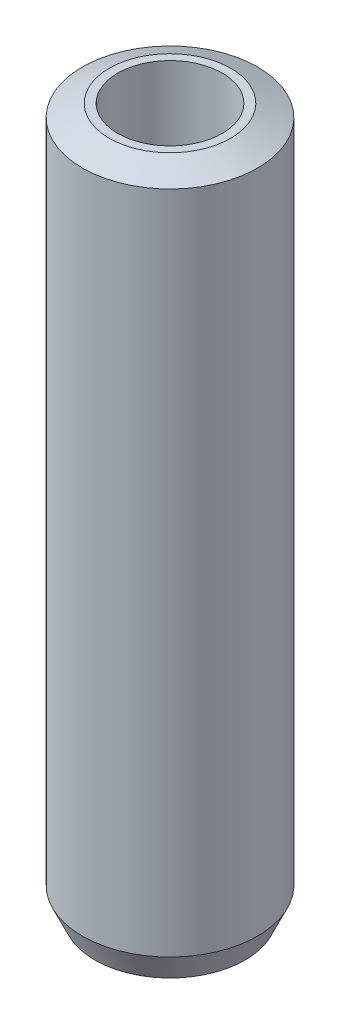
SolidWorks part; units mm, degrees
ref_plane "Front Plane" through (0, 0, 0) normal (0, 0, 1) x (1, 0, 0)
ref_plane "Top Plane" through (0, 0, 0) normal (0, 1, 0) x (1, 0, 0)
ref_plane "Right Plane" through (0, 0, 0) normal (1, 0, 0) x (0, 0, -1)
sketch "Sketch1" plane through (0, 0, 0) normal (0, 1, 0) x (1, 0, 0)
  circle A0 centre (0, 0) radius 37.5
  dimension "SHAFT_OD" = 75
extrude "Boss-Extrude1" add sketch "Sketch1" along normal blind 301.5153
sketch "Sketch2" plane through (0, 0, 0) normal (0, 1, 0) x (1, 0, 0)
  circle A0 centre (0, 0) radius 22.3756
  dimension "BORE_D" = 44.7511
extrude "Cut-Extrude1" cut sketch "Sketch2" along normal through all
chamfer "Chamfer1" distance 5.287 angle 65.341 2 edges at (0, 301.5153, 37.5) (0, 0, 37.5) first distance on face at (0, 301.5153, 37.5) first distance on face at (0, 0, 22.3756)
